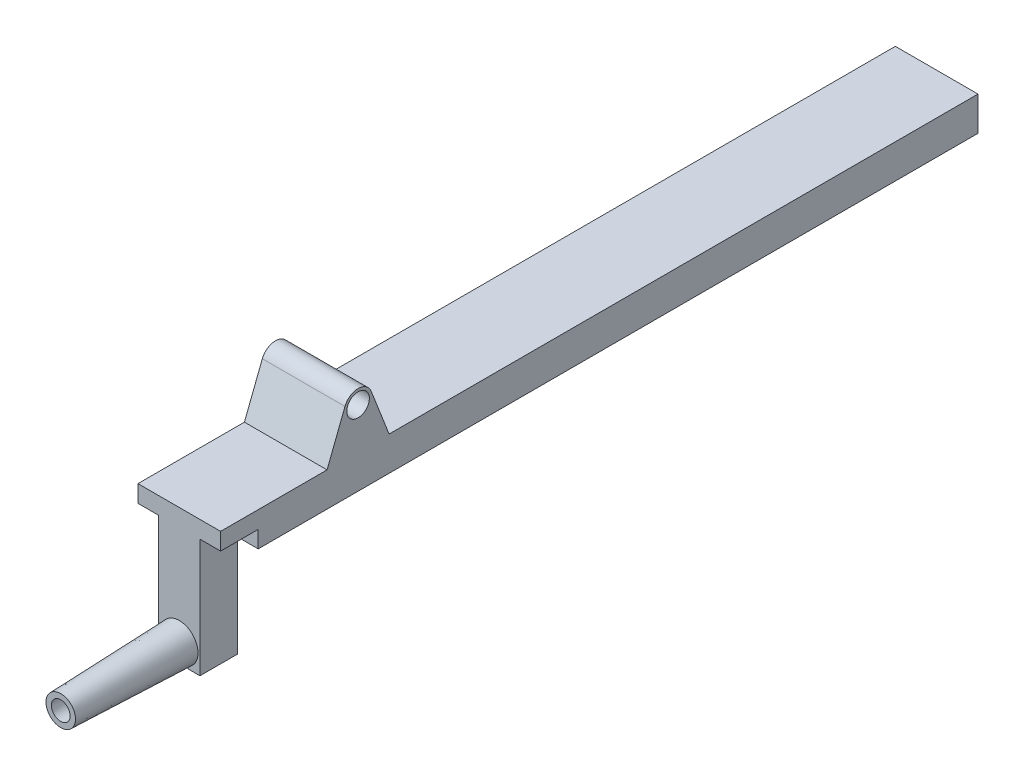
SolidWorks part; units mm, degrees
ref_plane "Front Plane" through (0, 0, 0) normal (0, 0, 1) x (1, 0, 0)
ref_plane "Top Plane" through (0, 0, 0) normal (0, 1, 0) x (1, 0, 0)
ref_plane "Right Plane" through (0, 0, 0) normal (1, 0, 0) x (0, 0, -1)
sketch "Sketch3" plane through (0, 0, 0) normal (1, 0, 0) x (0, 0, -1)
  line L1 (28.9563, -27.6098) -> (419.112, -27.6098) construction
  line L3 (419.112, -27.6098) -> (28.9563, -27.6098)
  line L4 (419.112, -27.6098) -> (419.112, -39.1795)
  line L5 (419.112, -39.1795) -> (-92.952, -39.1795)
  line L6 (-92.952, -27.6098) -> (-92.952, -39.1795)
  line L7 (0, 0) -> (0, -27.6098) construction
  line L9 (-28.959, -27.6098) -> (-92.952, -27.6098)
  line L10 (0, -27.6098) -> (-20.9804, -27.6098) construction
  line L12 (20.9804, -27.6098) -> (28.9563, -27.6098)
  line L13 (-28.959, -27.6098) -> (-20.9804, -27.6098)
  line L14 (-20.9804, -27.6098) -> (-8.8751, 3.4581)
  line L15 (20.9804, -27.6098) -> (8.8751, 3.4581)
  arc A0 (8.8751, 3.4581) -> (-8.8751, 3.4581) centre (0, 0) ccw
  circle A3 centre (0, 0) radius 7.62
  dimension "D1" = 512.064
  dimension "D3" = 27.6098
  dimension "D5" = 7.9786
  dimension "D2" = 63.993
  dimension "D4" = 11.5697
extrude "Boss-Extrude2" add sketch "Sketch3" along normal blind 27.94 and the other way blind 27.94
sketch "Sketch4" plane through (0, -39.1795, 0) normal (0, -1, 0) x (1, 0, 0)
  line L2 (0, 92.952) -> (0, 80.252) construction
  line L3 (-27.94, 92.952) -> (27.94, 92.952) construction
  line L5 (-13.97, 67.552) -> (13.97, 67.552)
  line L6 (-13.97, 67.552) -> (-13.97, 92.952)
  line L7 (-13.97, 92.952) -> (13.97, 92.952)
  line L8 (13.97, 67.552) -> (13.97, 92.952)
  line L9 (-13.97, 67.552) -> (13.97, 92.952) construction
  line L10 (-13.97, 92.952) -> (13.97, 67.552) construction
extrude "Boss-Extrude3" add sketch "Sketch4" along normal blind 80.01
sketch "Sketch5" plane through (0, 0, 67.552) normal (0, 0, -1) x (-1, 0, 0)
  line L2 (13.97, -119.1895) -> (-13.97, -119.1895) construction
  line L4 (6.0284, -117.6675) -> (6.0284, -119.1895)
  line L5 (6.0284, -119.1895) -> (0, -119.1895)
  line L6 (0, -116.459) -> (0, -96.52)
  arc A0 (0, -119.1895) -> (6.0284, -117.6675) centre (0, -106.4895) ccw
  arc A1 (0, -116.459) -> (0, -96.52) centre (0, -106.4895) ccw
extrude "Cut-Extrude4" cut sketch "Sketch5" against normal up to surface (25.4 mm away) up to face at (0, -56.2896, 92.952)
mirror "Mirror1" about plane through (0, -116.459, 115.2445) normal (1, 0, 0) of "Cut-Extrude4"
sketch "Sketch7" plane through (0, 0, 0) normal (1, 0, 0) x (0, 0, -1)
  line L0 (0, 0) -> (-173.1004, 0) construction
  line L2 (-92.952, -106.426) -> (-173.1004, -106.426) construction
  line L3 (-92.952, -119.1895) -> (-92.952, -39.1795) construction
  line L4 (-173.1004, -106.426) -> (-173.1004, 0) construction
ref_plane "Plane1" through (0, 0, 173.1004) normal (0, 0, 1) x (1, 0, 0)
sketch "Sketch9" plane through (0, 0, 173.1004) normal (0, 0, 1) x (1, 0, 0)
  circle A1 centre (0, -106.4895) radius 9.9695
sketch "Sketch10" plane through (0, 0, 92.952) normal (0, 0, 1) x (1, 0, 0)
  circle A1 centre (0, -106.4895) radius 12.7
loft "Loft1" add profiles "Sketch9", "Sketch10" connector at (9.9695, -106.4895, 173.1004) connector at (12.7, -106.4895, 92.952)
sketch "Sketch11" plane through (0, 0, 92.952) normal (0, 0, 1) x (1, 0, 0)
  circle A0 centre (0, -106.4895) radius 9.9695
sketch "Sketch12" plane through (0, 0, 173.1004) normal (0, 0, 1) x (1, 0, 0)
  circle A0 centre (0, -106.4895) radius 6.35
loft "Cut-Loft1" cut profiles "Sketch11", "Sketch12" connector at (9.9695, -106.4895, 92.952) connector at (6.35, -106.4895, 173.1004)
ref_axis "Axis1" through (-27.94, 0, 0) along (1, 0, 0)
sketch "Sketch14" plane through (0, -39.1795, 0) normal (0, -1, 0) x (1, 0, 0)
  line L0 (-27.94, 67.552) -> (27.94, 67.552)
  line L1 (-27.94, 92.952) -> (-27.94, -419.112) construction
  line L2 (27.94, 92.952) -> (27.94, -419.112) construction
  line L3 (27.94, 67.552) -> (27.94, -419.112)
  line L4 (27.94, -419.112) -> (-27.94, -419.112)
  line L5 (-27.94, -419.112) -> (-27.94, 67.552)
extrude "Boss-Extrude5" add sketch "Sketch14" along normal blind 11.43
